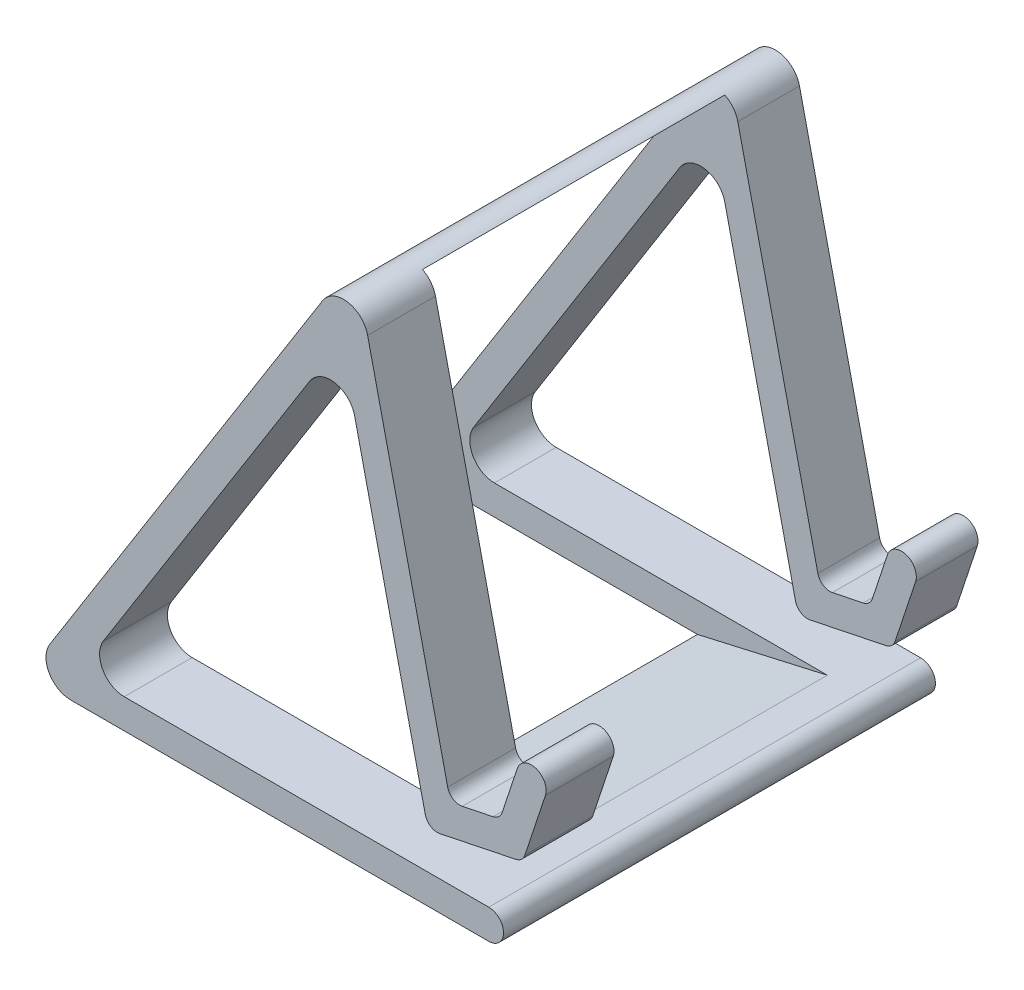
SolidWorks part; units mm, degrees
ref_plane "Front Plane" through (0, 0, 0) normal (0, 0, 1) x (1, 0, 0)
ref_plane "Top Plane" through (0, 0, 0) normal (0, 1, 0) x (1, 0, 0)
ref_plane "Right Plane" through (0, 0, 0) normal (1, 0, 0) x (0, 0, -1)
sketch "Sketch1" plane through (0, 0, 0) normal (0, 0, 1) x (1, 0, 0)
  line L0 (-38.2781, -20.7982) -> (-31.502, -20.7982)
  line L1 (-38.6167, -20.1853) -> (-34.1936, -13.1498)
  line L2 (-33.465, -13.2738) -> (-32.1672, -18.966)
  line L3 (-31.9317, -19.1174) -> (-31.4338, -19.0143)
  line L4 (-31.2844, -18.8812) -> (-31.0396, -18.1408)
  line L5 (-30.9157, -19.295) -> (-30.5839, -18.2915)
  line L6 (-32.295, -19.6829) -> (-31.065, -19.4281)
  line L7 (-33.6754, -14.5104) -> (-32.5306, -19.5315)
  line L8 (-37.7479, -19.7053) -> (-34.404, -14.3864)
  line L9 (-37.4093, -20.3182) -> (-31.502, -20.3182)
  line L10 (-33.6796, -12.3323) -> (-32.1236, -19.1572) construction
  line L11 (-39.002, -20.7982) -> (-33.6796, -12.3323) construction
  line L12 (-33.89, -13.5688) -> (-32.487, -19.7227) construction
  line L13 (-38.1333, -20.3182) -> (-33.89, -13.5688) construction
  line L14 (-38.1333, -20.3182) -> (-31.502, -20.3182) construction
  line L15 (-39.002, -20.7982) -> (-31.502, -20.7982) construction
  line L16 (-30.9519, -19.4046) -> (-30.5839, -18.2915) construction
  line L17 (-32.487, -19.7227) -> (-30.9519, -19.4046) construction
  line L18 (-31.3207, -18.9908) -> (-31.0396, -18.1408) construction
  line L19 (-32.1236, -19.1572) -> (-31.3207, -18.9908) construction
  arc A0 (-31.0396, -18.1408) -> (-30.5839, -18.2915) centre (-30.8118, -18.2162) cw
  arc A1 (-31.502, -20.3182) -> (-31.502, -20.7982) centre (-31.502, -20.5582) cw
  arc A2 (-33.465, -13.2738) -> (-34.1936, -13.1498) centre (-33.855, -13.3627) ccw
  arc A3 (-33.6754, -14.5104) -> (-34.404, -14.3864) centre (-34.0654, -14.5993) ccw
  arc A4 (-37.7479, -19.7053) -> (-37.4093, -20.3182) centre (-37.4093, -19.9182) ccw
  arc A5 (-38.6167, -20.1853) -> (-38.2781, -20.7982) centre (-38.2781, -20.3982) ccw
  arc A6 (-30.9157, -19.295) -> (-31.065, -19.4281) centre (-31.1056, -19.2322) cw
  arc A7 (-31.2844, -18.8812) -> (-31.4338, -19.0143) centre (-31.4743, -18.8184) cw
  arc A8 (-31.9317, -19.1174) -> (-32.1672, -18.966) centre (-31.9722, -18.9216) cw
  arc A9 (-32.295, -19.6829) -> (-32.5306, -19.5315) centre (-32.3356, -19.487) cw
  point P17 (-33.6796, -12.3323)
  point P33 (-31.3207, -18.9908)
  dimension "D7" = 0.4
  dimension "D1" = 0.2
  dimension "D2" = 45
  dimension "D8" = 120
  dimension "D5" = 0.48
extrude "Boss-Extrude1" add sketch "Sketch1" along normal mid plane 7 contours L8 A3 L7 A9 L6 A6 L5 A0 L4 A7 L3 A8 L2 A2 L1 A5 L0 A1 L9 A4
sketch "Sketch2" plane through (-18.5821, 11.6822, 0) normal (-0.8466, 0.5322, 0) x (0, 0, 1)
  line L0 (0, -37.777) -> (0, -37.7424) construction
  line L1 (0, -37.7424) -> (0, -32.6614) construction
sketch "Sketch3" plane through (-34.6882, -7.9084, 0) normal (0.975, 0.2223, 0) x (0, 0, -1)
  line L1 (-2.4, -5.194) -> (2.5, -5.194)
  line L2 (-2.4, -5.194) -> (-2.4, -12.694)
  line L3 (-2.4, -12.694) -> (2.5, -12.694)
  line L4 (2.5, -5.194) -> (2.5, -12.694)
  line L5 (-2.4, -5.194) -> (2.5, -12.694) construction
  line L6 (-2.4, -12.694) -> (2.5, -5.194) construction
  point P0 (0.05, -8.944)
  point P5 (0, 0)
  dimension "D1" = 7.5
  dimension "D2" = 1
  dimension "D3" = 1.1
extrude "Cut-Extrude1" cut sketch "Sketch3" against normal through all both and the other way through all
